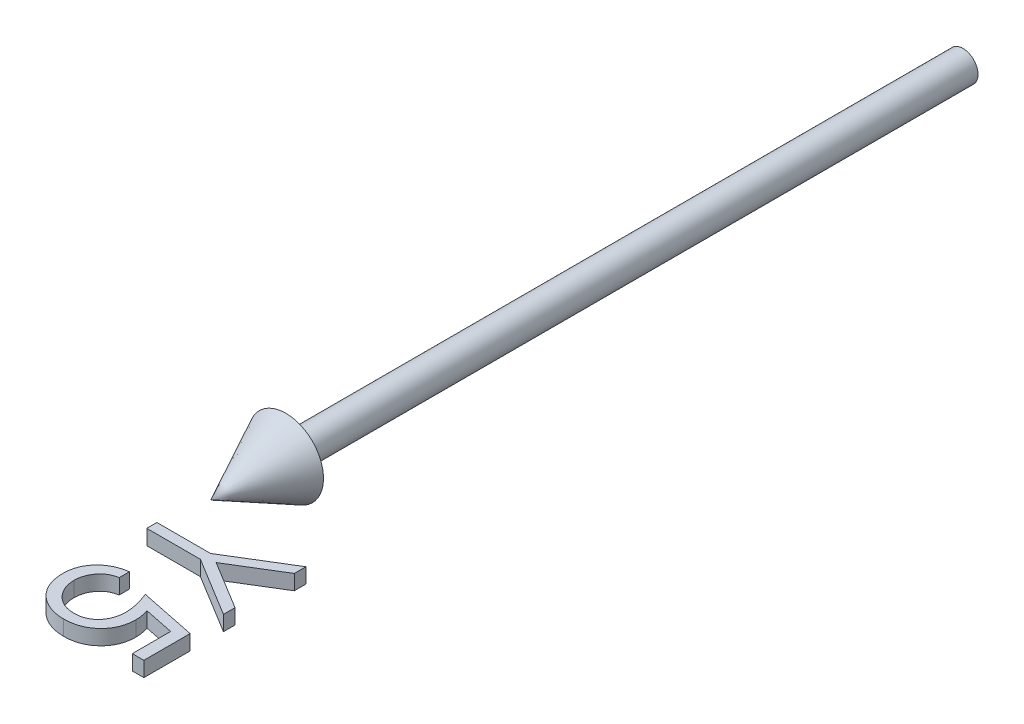
SolidWorks part; units mm, degrees
ref_plane "Front Plane" through (0, 0, 0) normal (0, 0, 1) x (1, 0, 0)
ref_plane "Top Plane" through (0, 0, 0) normal (0, 1, 0) x (1, 0, 0)
ref_plane "Right Plane" through (0, 0, 0) normal (1, 0, 0) x (0, 0, -1)
sketch "Sketch2" plane through (0, 0, 0) normal (0, 1, 0) x (1, 0, 0)
  line L0 (0, 41.95) -> (0, -114.4521) construction
  line L1 (-36.8894, 0) -> (41.4965, 0) construction
  line L2 (0, -100) -> (5, -90)
  line L3 (5, -90) -> (2, -90)
  line L4 (2, -90) -> (2, 0)
  line L5 (2, 0) -> (0, 0)
  line L6 (0, 0) -> (0, -100)
  dimension "D1" = 100
  dimension "D2" = 2
  dimension "D3" = 10
  dimension "D4" = 5
revolve "Revolve1" add sketch "Sketch2" angle 360 about L0
sketch "Sketch3" plane through (0, 0, 0) normal (0, 1, 0) x (1, 0, 0)
  line L0 (0, -101.5706) -> (0, -127.8138) construction
  text T0 "Y5\r\n\r\n\r\n" font "Century Gothic" height 15
extrude "Boss-Extrude1" add sketch "Sketch3" against normal blind 1 and the other way blind 1 separate body
equation "\"frame_arrow_length\"=100"
equation "\"D1@Sketch2\"=\"frame_arrow_length\""
equation "\"frame_arrow_odA\"=4"
equation "\"D2@Sketch2\"=\"frame_arrow_odA\"/2"
equation "\"frame_arrow_head_od\"=5"
equation "\"D4@Sketch2\"=\"frame_arrow_head_od\""
equation "\"frame_arrow_head_length\"=10"
equation "\"D3@Sketch2\"=\"frame_arrow_head_length\""
equation "\"tvarobot_theta1\"=30"
equation "\"link0_ringA_odA\"= 40"
equation "\"link0_ringA_odB\"= 25"
equation "\"link0_ringA_id\"= 20"
equation "\"link0_ringA_thickness\"= (\"link0_ringA_odB\" - \"link0_ringA_id\")/2"
equation "\"link0_ringA_height\"= 3"
equation "\"link0_ringA_heightA\"= 1.5"
equation "\"link0_ringA_heightB\"=\"link0_ringA_height\"-\"link0_ringA_heightA\""
equation "\"link0_ringB_odA\"= 40"
equation "\"link0_ringB_odB\"= 29"
equation "\"link0_ringB_id\"= \"link0_shaftA_bearing_id\"+1"
equation "\"link0_ringB_thickness\"= (\"link0_ringB_odB\" - \"link0_ringB_id\")/2"
equation "\"link0_ringB_height\"= 3"
equation "\"link0_ringB_heightA\"= 1.5"
equation "\"link0_ringB_heightB\"=\"link0_ringB_height\"-\"link0_ringB_heightA\""
equation "\"link0_shaftA_bearing_od\"=27"
equation "\"link0_shaftA_bearing_id\"=20"
equation "\"link0_shaftA_thrust_bearing_od\"=35"
equation "\"link0_shaftA_thrust_bearing_id\"=20.04"
equation "\"link0_shaftA_retaining_ring_id\"=18.5"
equation "\"link0_shaftA_retaining_ring_groove_width\"=1.5"
equation "\"link0_shaftA_spline_length\"=8.0"
equation "\"link0_shaftA_spline_depth\"=1.0"
equation "\"link0_shaftA_spline_width\"=4.0"
equation "\"link0_shaftA_odA\"=\"link0_shaftA_bearing_id\""
equation "\"link0_shaftA_odB\"=35"
equation "\"link0_shaftA_odC\"=\"link0_shaftA_bearing_id\""
equation "\"link0_shaftA_odD\"=\"link0_shaftA_odC\"-2*\"link0_shaftA_spline_depth\""
equation "\"link0_shaftA_odE\"=\"link0_shaftA_bearing_id\""
equation "\"link0_shaftA_odF\"=\"link0_shaftA_odE\"-2*\"link0_shaftA_spline_depth\""
equation "\"link0_shaftA_idA\"=10"
equation "\"link0_shaftA_idB\"=6"
equation "\"link0_shaftA_length\"=39.5"
equation "\"link0_shaftA_lengthA\"=8.0"
equation "\"link0_shaftA_lengthB\"=12.0"
equation "\"link0_shaftA_lengthC\"=35.0"
equation "\"link0_shaftA_lengthD\"=39.0"
equation "\"link0_shaftA_lengthE\"=\"link0_shaftA_length\"-\"link0_shaftA_lengthD\""
equation "\"link0_shaftA_offsetX\"=11"
equation "\"link0_shaftA_offsetY\"=0"
equation "\"link0_shaftA_bolt_pattern_dia\"=14"
equation "\"link0_motor_center_dist\"=26"
equation "\"link0_46t_pulley_spline_length\"=8"
equation "\"link0_46t_pulley_spline_depth\"=\"link0_shaftA_spline_depth\"*1.025"
equation "\"link0_46t_pulley_spline_width\"=\"link0_shaftA_spline_width\"*1.05"
equation "\"link0_46t_pulley_idA\"=\"link0_shaftA_bearing_id\"*1.025"
equation "\"link0_46t_pulley_idB\"=\"link0_46t_pulley_idA\"-2*\"link0_46t_pulley_spline_depth\""
equation "\"link0_shaftB_spline_length\"=10"
equation "\"link0_shaftB_spline_depth\"=1.0"
equation "\"link0_shaftB_spline_width\"=1.25"
equation "\"link0_shaftB_length\"=7"
equation "\"link0_shaftB_lengthA\"=1.5"
equation "\"link0_shaftB_lengthB\"=2.75"
equation "\"link0_shaftB_odA\"=32"
equation "\"link0_shaftB_odB\"=22"
equation "\"link0_shaftB_odC\"=20"
equation "\"link0_shaftB_idA\"=10"
equation "\"link0_shaftB_bolt_diameter\"=19"
equation "\"link0_shaftB_bearing_od\"=27"
equation "\"link0_shaftB_bearing_id\"=20"
equation "\"link0_motor_length\"=46.5"
equation "\"link0_motor_width\"=28.5"
equation "\"link0_motor_height\"=34"
equation "\"link0_motor_offset\"=8"
equation "\"link0_shellA_thickness\"=2.5"
equation "\"link0_shellB_thickness\"=\"link0_shellA_thickness\""
equation "\"link0_plateA_shellA_height\"=48"
equation "\"link0_shellA_width\" =\"link0_plateA_width\""
equation "\"link0_shellA_height\" = \"link0_plateA_shellA_height\"-\"link0_plateA_height\""
equation "\"link0_shellA_length\" = \"link0_plateA_lengthB\" "
equation "\"link0_shellB_length\"=\"link0_shellA_length\""
equation "\"link0_shellA_radius\" = 0.375*25.4"
equation "\"link0_shellA_radiusA\"= \"link0_plateA_radiusA\""
equation "\"link0_shellA_radiusB\"= \"link0_plateA_radiusB\""
equation "\"link0_shellA_radiusC\"= 3"
equation "\"link0_postA_height\"=7"
equation "\"link0_postA_width\"=16"
equation "\"link0_postA_length\"=20"
equation "\"link0_postA_posX\"=22"
equation "\"link0_postA_posY\"=17.5"
equation "\"link0_postA_pocket_width\"=6.0"
equation "\"link0_postA_pocket_length\"=2.5"
equation "\"link0_postA_pocket_depth\"=9"
equation "\"link0_postA_pocket_posZ\"=10"
equation "\"link0_postB_height\"=7"
equation "\"link0_postB_width\"=16"
equation "\"link0_postB_length\"=20"
equation "\"link0_postB_posX\"=22"
equation "\"link0_postB_posY\"=17.5"
equation "\"link0_postB_id\"=3.0"
equation "\"link0_postB_pocket_width\"=6.0"
equation "\"link0_postB_pocket_length\"=2.5"
equation "\"link0_postB_pocket_depth\"=9"
equation "\"link0_postB_pocket_posZ\"=10"
equation "\"link0_postC_height\"=7"
equation "\"link0_postC_width\"=16"
equation "\"link0_postC_length\"=20"
equation "\"link0_postC_posX\"=22"
equation "\"link0_postC_posY\"=17.5"
equation "\"link0_postC_id\"=3.0"
equation "\"link0_postC_pocket_width\"=6.0"
equation "\"link0_postC_pocket_length\"=2.5"
equation "\"link0_postC_pocket_depth\"=9"
equation "\"link0_postC_pocket_posZ\"=10"
equation "\"link0_postD_height\"=7"
equation "\"link0_postD_width\"=16"
equation "\"link0_postD_length\"=20"
equation "\"link0_postD_posX\"=22"
equation "\"link0_postD_posY\"=17.5"
equation "\"link0_postD_id\"=3.0"
equation "\"link0_postD_pocket_width\"=6.0"
equation "\"link0_postD_pocket_length\"=3.0"
equation "\"link0_postD_pocket_depth\"=9"
equation "\"link0_postD_pocket_posZ\"=10"
equation "\"link0_postE_height\"=5"
equation "\"link0_postE_width\"=16"
equation "\"link0_postE_length\"=\"link0_plateE_lengthA\"-\"link0_lip_height\""
equation "\"link0_postE_posZ\"=22"
equation "\"link0_postE_posX\"=17.5"
equation "\"link0_postE_posY\"=22"
equation "\"link0_postE_id\"=3.0"
equation "\"link0_postE_cbore_id\"=6.5"
equation "\"link0_postE_hole_id\"=3"
equation "\"link0_postF_posZ\"=22"
equation "\"link0_postF_posX\"=17.5"
equation "\"link0_postF_posY\"=\"link0_plateB_lengthA\"+4"
equation "\"link0_postF_id\"=3.0"
equation "\"link0_postF_cbore_id\"=6.5"
equation "\"link0_postF_hole_id\"=3"
equation "\"link0_postG_posZ\"=22"
equation "\"link0_postG_posX\"=17.5"
equation "\"link0_postG_posY\"=\"link0_plateB_lengthA\"+12"
equation "\"link0_postG_id\"=3.0"
equation "\"link0_postG_cbore_id\"=6.5"
equation "\"link0_postG_hole_id\"=3"
equation "\"link0_postHIJ_posY\"=6"
equation "\"link0_postH_posX\"=28"
equation "\"link0_postH_posY\"=20"
equation "\"link0_postH_posZ\"=20"
equation "\"link0_postH_length\"=10"
equation "\"link0_postI_posX\"=28"
equation "\"link0_postI_posY\"=20"
equation "\"link0_postI_posZ\"=135"
equation "\"link0_postI_length\"=10"
equation "\"link0_postJ_posX\"=28"
equation "\"link0_postJ_posY\"=20"
equation "\"link0_postJ_posZ\"=175"
equation "\"link0_postJ_length\"=10"
equation "\"link0_postK_posX\"=28"
equation "\"link0_postK_posY\"=20"
equation "\"link0_postK_posZ\"=175"
equation "\"link0_postK_length\"=10"
equation "\"link0_postL_posX\"=28"
equation "\"link0_postL_posY\"=20"
equation "\"link0_postL_posZ\"=135"
equation "\"link0_postL_length\"=10"
equation "\"link0_postM_posX\"=28"
equation "\"link0_postM_posY\"=20"
equation "\"link0_postM_posZ\"=35"
equation "\"link0_postM_length\"=10"
equation "\"link0_plateA_lengthA\"=30"
equation "\"link0_plateA_lengthB\"=150"
equation "\"link0_plateA_lengthC\"=30"
equation "\"link0_plateA_length\"=\"link0_plateA_lengthA\"+\"link0_plateA_lengthB\"+\"link0_plateA_lengthC\""
equation "\"link0_plateA_width\"=  68"
equation "\"link0_plateA_height\"= \"link0_plateA_radiusA\""
equation "\"link0_plateA_thickness\"=\"link0_shellA_thickness\""
equation "\"link0_plateA_radius\"= 9.5"
equation "\"link0_plateA_radiusA\"= 18"
equation "\"link0_plateA_radiusB\"= 18"
equation "\"link0_plateA_radiusC\"= 3"
equation "\"link0_plateB_length\"= 40"
equation "\"link0_plateB_width\"= \"link0_plateA_width\"*1.005"
equation "\"link0_plateB_height\"= \"link0_plateA_shellA_height\"*1.005"
equation "\"link0_plateB_lengthA\"=\"link0_lip_height\"+\"link0_plateD_thickness\"+\"link0_motor_mount_thickness\""
equation "\"link0_plateB_lengthB\"=\"link0_plateB_height\"-\"link0_plateB_lengthA\""
equation "\"link0_plateB_radiusA\"= \"link0_plateA_radiusA\""
equation "\"link0_plateB_radiusB\"= \"link0_plateA_radiusB\""
equation "\"link0_plateB_radiusC\"= 3"
equation "\"link0_plateB_idA\"=\"link0_shaftA_odC\"+1"
equation "\"link0_plateB_idB\"=\"link0_shaftA_bearing_od\"-2"
equation "\"link0_plateB_idC\"=\"link0_shaftA_bearing_od\"*1.005"
equation "\"link0_plateB_idD\"=\"link0_shaftA_thrust_bearing_od\"+1 "
equation "\"link0_plateB_depthA\"=1.0"
equation "\"link0_plateB_depthB\"=2.0"
equation "\"link0_plateB_depthC\"=8"
equation "\"link0_plateB_depthD\"=\"link0_plateB_length\"-\"link0_lip_height\"-\"link0_plateD_thickness\" "
equation "\"link0_plateC_length\"=\"link0_plateB_length\""
equation "\"link0_plateC_width\"= \"link0_plateB_width\""
equation "\"link0_plateC_height\"= .1*25.4"
equation "\"link0_plateA_hole_od\" = 0.1*25.4"
equation "\"link0_plateA_hole_delx\" = 0.5*25.4"
equation "\"link0_plateA_hole_delz\" = 0.75*25.4"
equation "\"link0_plateA_hole_offx\" = 0.0*25.4"
equation "\"link0_plateA_hole_offz\" = \"link0_plateA_length\"/2"
equation "\"link0_plateB_hole_od\" = 0.1*25.4"
equation "\"link0_plateB_hole_delx\"= 0.75*25.4"
equation "\"link0_plateB_hole_delz\"= 0.75*25.4"
equation "\"link0_plateB_hole_offx\"= 0.0*25.4"
equation "\"link0_plateB_hole_offz\"= 0.0*25.4"
equation "\"link0_plateC_hole_od\"= 0.1*25.4"
equation "\"link0_plateC_hole_delx\"= 0.75*25.4"
equation "\"link0_plateC_hole_delz\"= 0.75*25.4"
equation "\"link0_plateC_hole_offx\"= 0.0*25.4"
equation "\"link0_plateC_hole_offz\"= 0.0*25.4"
equation "\"link0_plateD_height\"=\"link0_plateB_height\"-2*\"link0_shellA_thickness\""
equation "\"link0_plateD_width\"=\"link0_plateB_width\"-2*\"link0_shellA_thickness\""
equation "\"link0_plateD_thickness\"=10"
equation "\"link0_plateD_radiusA\"=\"link0_plateB_radiusA\"-\"link0_shellA_thickness\""
equation "\"link0_plateD_odA\"= .375*25.4"
equation "\"link0_plateD_odB\"= .375*25.4"
equation "\"link0_plateD_bearing_id\"=20"
equation "\"link0_plateD_bearing_od\"=27"
equation "\"link0_plateE_radiusA\"=\"link0_plateA_radiusA\""
equation "\"link0_plateE_radiusB\"=\"link0_plateA_radiusB\""
equation "\"link0_plateE_radiusC\"=8.0"
equation "\"link0_plateE_length\"=30"
equation "\"link0_plateE_lengthA\"=16"
equation "\"link0_plateE_height\"=\"link0_plateB_height\""
equation "\"link0_plateE_width\"=\"link0_plateB_width\""
equation "\"link0_plateE_odA\"=\"gantry_coupler_id\"*0.99"
equation "\"link0_plateE_idA\"=\"link0_plateE_odA\"-20.0"
equation "\"link0_plateE_spline_depth\"=\"link0_poleA_spline_depth\"*1.05"
equation "\"link0_plateE_spline_width\"=\"link0_poleA_spline_width\"*1.075"
equation "\"link0_plateE_spline_length\"=\"link0_poleA_spline_length\""
equation "\"link0_plateE_coupler_length\"=46"
equation "\"link0_lip_height\"=5.0"
equation "\"link0_lip_thickness\"=2.0"
equation "\"link0_motor_mount_thickness\"=8.0"
equation "\"link0_motor_mount_idA\"=22"
equation "\"link0_motor_mount_idB\"=\"link0_shaftB_bearing_od\"*1.005"
equation "\"link0_motor_mount_idC\"=\"link0_shaftB_bearing_od\"-2"
equation "\"link0_motor_mount_depthA\"=5.5"
equation "\"link0_motor_mount_height\"=\"link0_plateD_height\""
equation "\"link0_motor_mount_width\"=\"link0_plateD_width\""
equation "\"link0_motor_mountL_height\"=36"
equation "\"link0_motor_mountL_heightA\"=12"
equation "\"link0_motor_mountL_length\"=50"
equation "\"link0_motor_mountL_lengthA\"=36"
equation "\"gantry_coupler_od\"=25.4*2.0"
equation "\"gantry_coupler_id\"=1.645*25.4"
equation "\"gantry_coupler_offsetX\"=\"link0_plateE_width\"/2"
equation "\"link0_poleA_odA\"=20"
equation "\"link0_poleA_odB\"=36"
equation "\"link0_poleA_idA\"=\"link0_poleA_odA\"-2*\"link0_poleA_thickness\""
equation "\"link0_poleA_idB\"=(\"link0_plateE_idA\"/2+1.5*\"link0_lip_thickness\")*1.04"
equation "\"link0_poleA_thickness\"=3.5"
equation "\"link0_poleA_length\"=100"
equation "\"link0_poleA_lengthA\"=18.5"
equation "\"link0_poleA_lengthB\"=80"
equation "\"link0_poleA_gasket_thickness\"=1.5"
equation "\"link0_poleA_spline_depth\"=1.0"
equation "\"link0_poleA_spline_width\"=4.0"
equation "\"link0_poleA_spline_length\"=10.0"
equation "\"link1_plateB_length\"=30"
equation "\"link1_lip_height\"=\"link0_lip_height\""
equation "\"link0_tension_plateA_width\"=12"
equation "\"link0_tension_plateA_lengthA\"=10.5"
equation "\"link0_tension_plateB_width\"=\"link0_tension_plateA_width\""
equation "\"link0_tension_plateB_lengthA\"=\"link0_tension_plateA_lengthA\""
equation "\"link0_tension_wheelA_posZ\"=7"
equation "\"link0_tension_wheelA_posX\"=\"link0_plateD_height\"/2-\"link0_tension_plateA_lengthA\""
equation "\"link0_m2_clear_hole_id\"=2.35"
equation "\"link0_m2_insert_hole_id\"=2.5"
equation "\"link0_m2_tap_hole_id\"=1.75"
equation "\"link0_m2_nut_socket_width\"=4.25"
equation "\"link0_m2_nut_socket_depth\"=2.5"
equation "\"link0_m2_cbore_id\"=3.75"
equation "\"link0_m2_cbore_depth\"=7"
equation "\"link0_m2_5_clear_hole_id\"=2.75"
equation "\"link0_m2_5_insert_hole_id\"=2.75"
equation "\"link0_m2_5_tap_hole_id\"=2.25"
equation "\"link0_m2_5_nut_socket_width\"=5.25"
equation "\"link0_m2_5_nut_socket_depth\"=2.5"
equation "\"link0_m2_5_cbore_id\"=4.75"
equation "\"link0_m2_5_cbore_depth\"=2.5"
equation "\"link0_m2_5_insert_access_length\"=6.0"
equation "\"link0_m2_5_insert_access_width\"=3.0"
equation "\"link0_m3_clear_hole_id\"=3.25"
equation "\"link0_m3_insert_hole_id\"=3"
equation "\"link0_m3_tap_hole_id\"=2.75"
equation "\"link0_m3_nut_socket_width\"=5.75"
equation "\"link0_m3_nut_socket_depth\"=4.0"
equation "\"link0_m3_cbore_id\"=5.75"
equation "\"link0_m3_cbore_depth\"=3.5"
equation "\"link0_m3_insert_access_length\"=4.5"
equation "\"link0_m3_insert_access_width\"=3.5"
equation "\"link0_rpi_mount_height\"=6"
equation "\"link0_rpi_mount_width\"=49"
equation "\"link0_rpi_mount_length\"=58"
equation "\"link0_rpi_mount_post_od\"=6"
equation "\"link0_rpi_mount_posZ\"=72"
equation "\"link0_rpi_mount_posX\"=11.5"
equation "\"link0_mcu_mount_height\"=5"
equation "\"link0_mcu_mount_width\"=49"
equation "\"link0_mcu_mount_length\"=58"
equation "\"link0_mcu_mount_post_od\"=6"
equation "\"link0_mcu_mount_posZ\"=164"
equation "\"link0_mcu_mount_posX\"=4"
equation "\"link0_pwr_mount_height\"=4"
equation "\"link0_pwr_mount_width\"=15.75"
equation "\"link0_pwr_mount_length\"=75.75"
equation "\"link0_pwr_mount_post_od\"=6"
equation "\"link0_pwr_mount_posZ\"=75"
equation "\"link0_pwr_mount_posX\"=16"
equation "\"link0_pwr_board_height\"=6"
equation "\"link0_pwr_board_width\"=21"
equation "\"link0_pwr_board_length\"=80"
